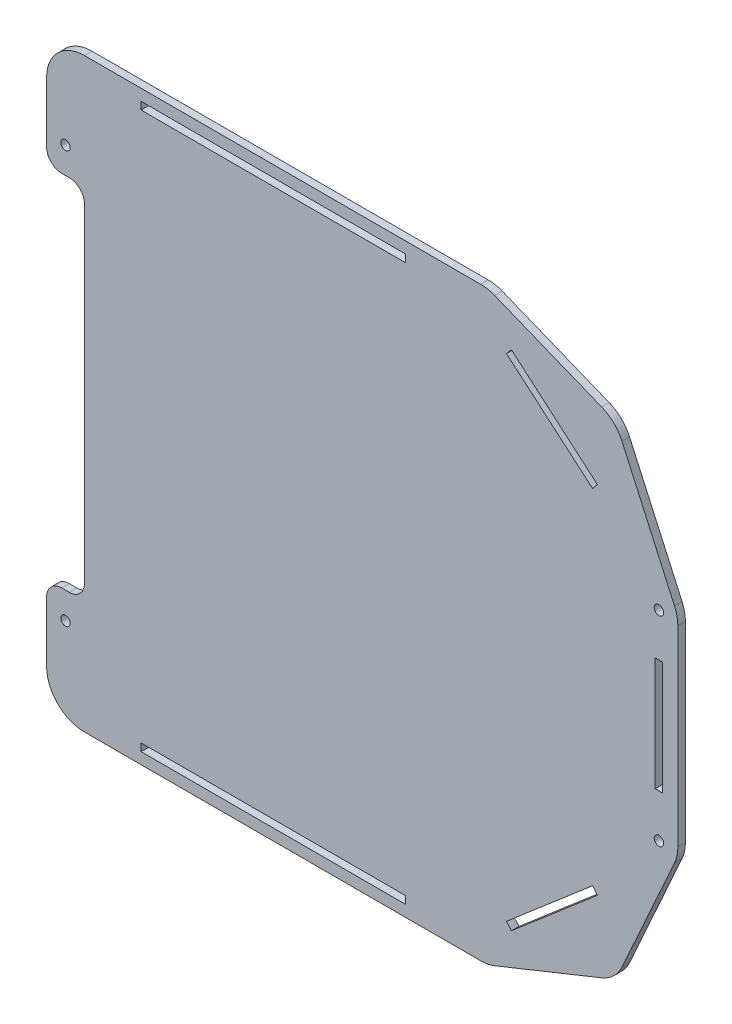
SolidWorks part; units mm, degrees
material "PVC rigido"
ref_plane "Piano frontale" through (0, 0, 0) normal (0, 0, 1) x (1, 0, 0)
ref_plane "Piano superiore" through (0, 0, 0) normal (0, 1, 0) x (1, 0, 0)
ref_plane "Piano destro" through (0, 0, 0) normal (1, 0, 0) x (0, 0, -1)
sketch "Schizzo1" plane through (0, 0, 0) normal (0, 0, 1) x (1, 0, 0)
  line L0 (25.7647, -77.5) -> (59.5674, -63.9093)
  line L1 (-91, -77.5) -> (25.7647, -77.5)
  line L2 (-91, -77.5) -> (-91, 77.5)
  line L3 (-91, 77.5) -> (25.7647, 77.5)
  line L4 (76, -27.5) -> (76, 27.5)
  line L5 (69.2392, 67.1366) -> (85.1147, 31.9616) construction
  line L6 (59.5674, -63.9093) -> (59.5674, 63.9093) construction
  line L7 (59.5674, -63.9093) -> (76, -27.5)
  line L8 (25.7647, 77.5) -> (59.5674, 63.9093)
  line L9 (59.5674, 63.9093) -> (76, 27.5)
  line L10 (25.7647, 77.5) -> (76, 77.5) construction
  line L11 (76, 77.5) -> (76, 27.5) construction
  line L12 (25.7647, -77.5) -> (76, -77.5) construction
  line L13 (76, -77.5) -> (76, -27.5) construction
  line L14 (63.8549, -72.3011) -> (27.8474, -86.7782) construction
  line L15 (85.1147, -31.9616) -> (69.2392, -67.1366) construction
  line L16 (27.8474, 86.7782) -> (63.8549, 72.3011) construction
  line L17 (0, 0) -> (25.7647, 77.5) construction
  line L18 (0, 0) -> (25.7647, -77.5) construction
  line L19 (25.7647, -77.5) -> (25.7647, 77.5) construction
  line L20 (-91, -77.5) -> (0, 0) construction
  line L21 (0, 0) -> (-91, 77.5) construction
  line L22 (0, 0) -> (-91, 0) construction
  line L23 (0, 0) -> (0, 77.5) construction
  line L24 (86, 27.8479) -> (86, -27.8479) construction
  point P0 (0, 0)
  dimension "D1" = 155
  dimension "D2" = 91
  dimension "D3" = 55
  dimension "D4" = 10
extrude "Estrusione-Estrusione1" add sketch "Schizzo1" along normal blind 2
hole_wizard "Foro filettato M3x0.5-1" positions "Schizzo3" profile "Schizzo2" tap size "M3x0.5" standard "Ansi Metric" end condition through all
sketch "Schizzo3" plane through (0, 0, 0) normal (0, 0, -1) x (-1, 0, 0)
  line L0 (86, -77.5) -> (86, -54.5) construction
  line L1 (91, -77.5) -> (-25.7647, -77.5) construction
  line L2 (86, -54.5) -> (86, 54.5) construction
  line L3 (86, 54.5) -> (86, 77.5) construction
  line L4 (-25.7647, 77.5) -> (91, 77.5) construction
  line L6 (0, 0) -> (86, 0) construction
  point P0 (86, -54.5)
  point P2 (86, 54.5)
sketch "Schizzo2" plane through (-86, -54.5, 0) normal (1, 0, 0) x (0, 1, 0)
  line L0 (0, 0) -> (0, 2)
  line L1 (0, 2) -> (1.25, 2)
  line L2 (1.25, 2) -> (1.25, 0)
  line L5 (1.25, 0) -> (0, 0)
  line L11 (0, -6.35) -> (0, 107.95) construction
  dimension "Thru Tap Drill Dia." = 2.5
  dimension "Thru Tap Drill Depth" = 2
cosmetic thread "Filettatura del foro1" parameters "D2"=3
cosmetic thread "Filettatura del foro2" parameters "D2"=3
sketch "Schizzo4" plane through (0, 0, 0) normal (0, 0, -1) x (-1, 0, 0)
  line L0 (31, -72.5) -> (31, 72.5) construction
  line L1 (66, -74.5) -> (-4, -74.5)
  line L2 (66, -74.5) -> (66, -72.5)
  line L3 (66, -72.5) -> (-4, -72.5)
  line L4 (-4, -74.5) -> (-4, -72.5)
  line L5 (66, 72.5) -> (-4, 72.5)
  line L6 (66, 72.5) -> (66, 74.5)
  line L7 (66, 74.5) -> (-4, 74.5)
  line L8 (-4, 72.5) -> (-4, 74.5)
  line L9 (31, 0) -> (91, 0) construction
  line L10 (91, 77.5) -> (91, -77.5) construction
  line L11 (91, -77.5) -> (-25.7647, -77.5) construction
  dimension "D1" = 2
  dimension "D2" = 3
  dimension "D3" = 70
  dimension "D4" = 60
extrude "Taglio-Estrusione1" cut sketch "Schizzo4" against normal blind 10
hole_wizard "Foro filettato M3x0.5-2" positions "Schizzo6" profile "Schizzo5" tap size "M3x0.5" standard "Ansi Metric" end condition through all
sketch "Schizzo6" plane through (0, 0, 2) normal (0, 0, 1) x (1, 0, 0)
  line L16 (55.0101, -61.8525) -> (71, -26.4239)
  line L17 (71, -26.4239) -> (71, 26.4239)
  line L18 (71, 26.4239) -> (55.0101, 61.8525)
  line L19 (55.0101, -61.8525) -> (71, -26.4239) construction
  line L20 (71, -26.4239) -> (71, 26.4239) construction
  line L21 (71, 26.4239) -> (55.0101, 61.8525) construction
  point P0 (71, 26.4239)
  point P2 (71, -26.4239)
  dimension "D1" = 5
sketch "Schizzo5" plane through (71, 26.4239, 2) normal (1, 0, 0) x (0, -1, 0)
  line L0 (0, 0) -> (0, 2)
  line L1 (0, 2) -> (1.25, 2)
  line L2 (1.25, 2) -> (1.25, 0)
  line L5 (1.25, 0) -> (0, 0)
  line L11 (0, -6.35) -> (0, 107.95) construction
  dimension "Thru Tap Drill Dia." = 2.5
  dimension "Thru Tap Drill Depth" = 2
cosmetic thread "Filettatura del foro3" parameters "D2"=3
cosmetic thread "Filettatura del foro4" parameters "D2"=3
sketch "Schizzo7" plane through (0, 0, 2) normal (0, 0, 1) x (1, 0, 0)
  line L0 (31.9679, 66.557) -> (54.746, 47.0338)
  line L1 (53.4445, 45.5153) -> (30.6663, 65.0385)
  line L2 (30.6663, 65.0385) -> (31.9679, 66.557)
  line L3 (53.4445, 45.5153) -> (54.746, 47.0338)
  line L4 (71, 26.4239) -> (4, 73.5) construction
  line L5 (4, 74.5) -> (4, 72.5) construction
  line L6 (4, 74.5) -> (4, 72.5) construction
  line L7 (31.3171, 65.7977) -> (54.0953, 46.2746) construction
  line L8 (42.7062, 56.0361) -> (37.5, 49.962) construction
  line L9 (71, 26.4239) -> (71, 15) construction
  line L10 (71, 15) -> (71, -15) construction
  line L11 (71, -15) -> (71, -26.4239) construction
  line L12 (71, -26.4239) -> (4, -73.5) construction
  line L13 (59.5674, -63.9093) -> (42.7062, -56.0361) construction
  line L14 (54.0953, -46.2746) -> (76, -27.5) construction
  line L15 (4, -72.5) -> (4, -74.5) construction
  line L16 (53.4445, -45.5153) -> (30.6663, -65.0385)
  line L17 (30.6663, -65.0385) -> (31.9679, -66.557)
  line L18 (31.9679, -66.557) -> (54.746, -47.0338)
  line L19 (54.746, -47.0338) -> (53.4445, -45.5153)
  line L20 (54.0953, -46.2746) -> (31.3171, -65.7977) construction
  line L21 (37.5, -49.962) -> (42.7062, -56.0361) construction
  line L22 (76, 27.5) -> (54.0953, 46.2746) construction
  line L23 (72, -15) -> (70, -15)
  line L24 (72, -15) -> (72, 15)
  line L25 (72, 15) -> (70, 15)
  line L26 (70, -15) -> (70, 15)
  dimension "D1" = 30
  dimension "D2" = 8
  dimension "D3" = 30
extrude "Taglio-Estrusione2" cut sketch "Schizzo7" against normal blind 10
sketch "Schizzo8" plane through (0, 0, 2) normal (0, 0, 1) x (1, 0, 0)
  line L0 (-91, 77.5) -> (-91, -77.5) construction
  line L1 (-91, -47.5) -> (-81, -47.5)
  line L2 (-91, -47.5) -> (-91, 47.5)
  line L3 (-91, 47.5) -> (-81, 47.5)
  line L4 (-81, -47.5) -> (-81, 47.5)
  line L5 (-86, -54.5) -> (-86, -47.5) construction
  line L6 (-86, 54.5) -> (-86, 47.5) construction
  dimension "D1" = 95
extrude "Taglio-Estrusione3" cut sketch "Schizzo8" against normal blind 10
fillet "Raccordo1" radius 10 2 edges at (-91, 77.5, 1) (-91, -77.5, 1)
fillet "Raccordo2" radius 10 6 edges at (25.7647, -77.5, 1) (59.5674, -63.9093, 1) (76, -27.5, 1) (76, 27.5, 1) (59.5674, 63.9093, 1) (25.7647, 77.5, 1)
fillet "Raccordo3" radius 4 4 edges at (-81, 47.5, 1) (-91, 47.5, 1) (-81, -47.5, 1) (-91, -47.5, 1)
